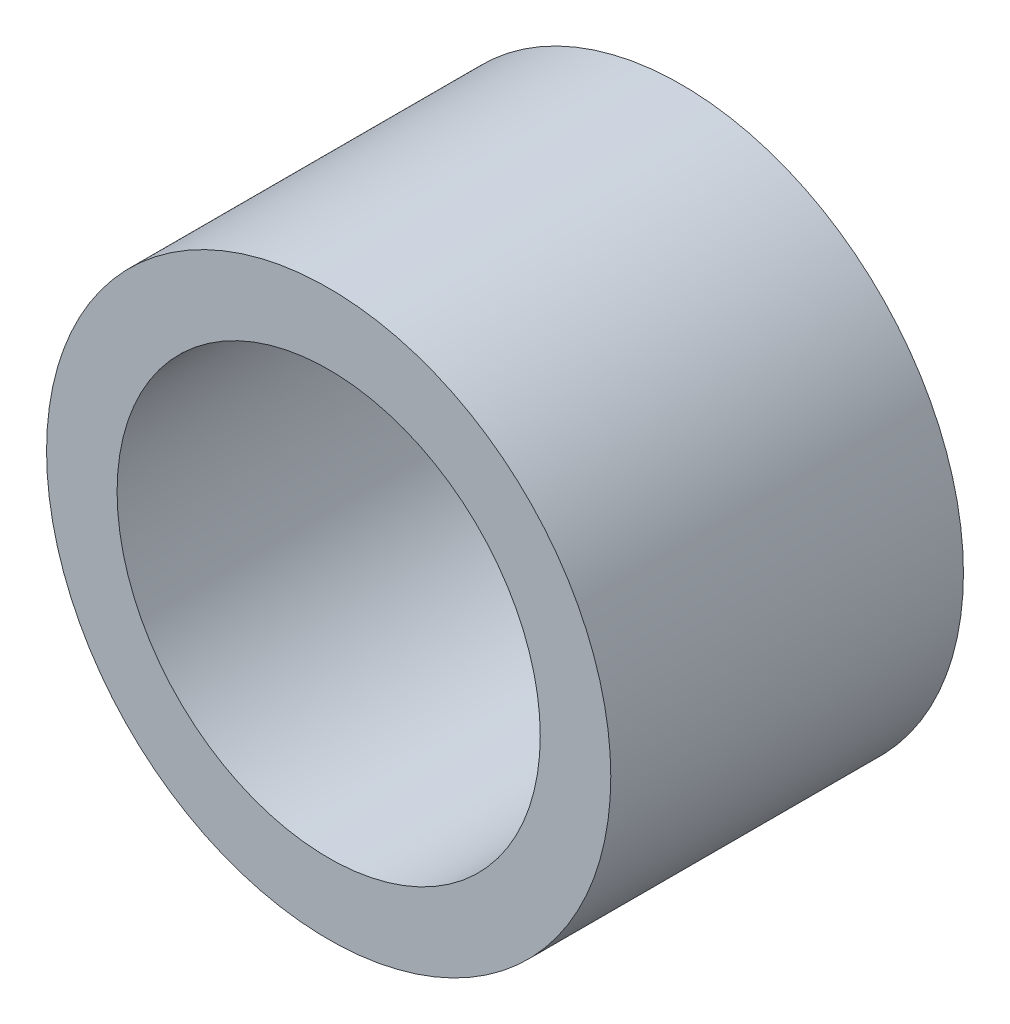
SolidWorks part; units mm, degrees
ref_plane "前视基准面" through (0, 0, 0) normal (0, 0, 1) x (1, 0, 0)
ref_plane "上视基准面" through (0, 0, 0) normal (0, 1, 0) x (1, 0, 0)
ref_plane "右视基准面" through (0, 0, 0) normal (1, 0, 0) x (0, 0, -1)
sketch "草图1" plane through (0, 0, 0) normal (0, 0, 1) x (1, 0, 0)
  circle A0 centre (0, 0) radius 3
  circle A1 centre (0, 0) radius 4
extrude "凸台-拉伸1" add sketch "草图1" along normal blind 5
extrude "凸台-拉伸2" add sketch "草图1<2>" along normal blind 5
sketch "草图1<2>" plane through (0, 0, 0) normal (0, 0, 1) x (1, 0, 0) same geometry as "草图1"
